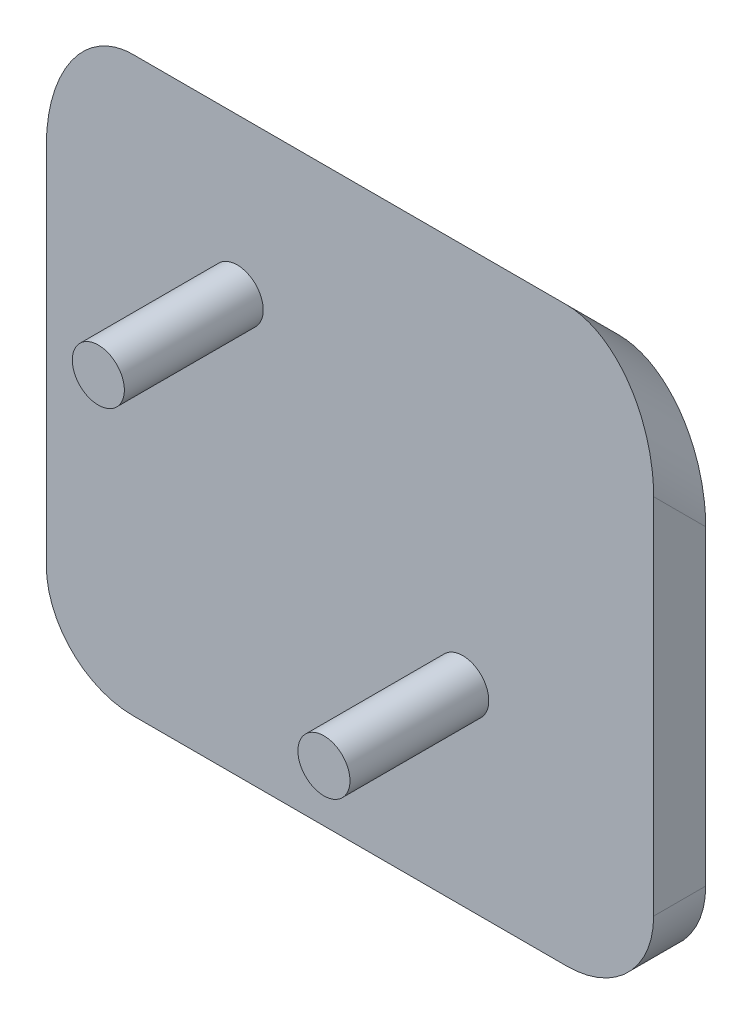
SolidWorks part; units mm, degrees
ref_plane "Front Plane" through (0, 0, 0) normal (0, 0, 1) x (1, 0, 0)
ref_plane "Top Plane" through (0, 0, 0) normal (0, 1, 0) x (1, 0, 0)
ref_plane "Right Plane" through (0, 0, 0) normal (1, 0, 0) x (0, 0, -1)
sketch "Sketch1" plane through (0, 0, 0) normal (0, 0, 1) x (1, 0, 0)
  line L1 (0, 0) -> (35, 0)
  line L2 (0, 0) -> (0, 35)
  line L3 (0, 35) -> (35, 35)
  line L4 (35, 0) -> (35, 35)
  dimension "D1" = 35
  dimension "D2" = 35
extrude "Boss-Extrude1" add sketch "Sketch1" along normal blind 3
sketch "Sketch2" plane through (0, 0, 3) normal (0, 0, 1) x (1, 0, 0)
  line L0 (35, 0) -> (35, 35) construction
  line L1 (0, 0) -> (35, 0) construction
  line L2 (35, 35) -> (0, 35) construction
  line L3 (0, 35) -> (0, 0) construction
  circle A0 centre (11, 24) radius 1.5
  circle A1 centre (24, 11) radius 1.5
  dimension "D1" = 3
  dimension "D2" = 3
  dimension "D3" = 11
  dimension "D4" = 11
  dimension "D5" = 11
  dimension "D6" = 11
extrude "Boss-Extrude2" add sketch "Sketch2" along normal blind 8
chamfer "Chamfer1" distance 5 angle 45 1 edges at (17.5, 35, 0)
fillet "Fillet1" radius 5 4 edges at (0, 0, 1.5) (35, 0, 1.5) (35, 31.5, 1.5) (0, 31.5, 1.5)
